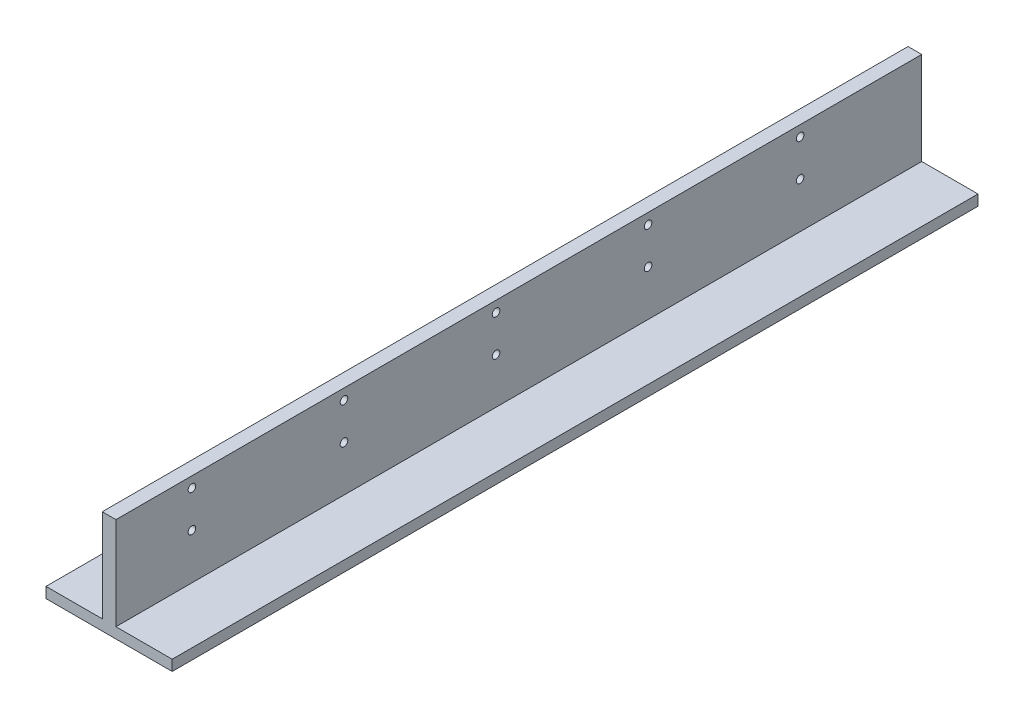
SolidWorks part; units mm, degrees
ref_plane "Plan de face" through (0, 0, 0) normal (0, 0, 1) x (1, 0, 0)
ref_plane "Plan de dessus" through (0, 0, 0) normal (0, 1, 0) x (1, 0, 0)
ref_plane "Plan de droite" through (0, 0, 0) normal (1, 0, 0) x (0, 0, -1)
sketch "Esquisse1" plane through (0, 0, 0) normal (0, 0, 1) x (1, 0, 0)
  line L0 (0, 0) -> (83, 0)
  line L1 (83, 0) -> (83, 7)
  line L2 (83, 7) -> (46, 7)
  line L3 (46, 7) -> (46, 68)
  line L4 (46, 68) -> (37, 68)
  line L5 (37, 68) -> (37, 7)
  line L6 (37, 7) -> (0, 7)
  line L7 (0, 7) -> (0, 0)
  dimension "D1" = 7
  dimension "D2" = 9
  dimension "D3" = 83
  dimension "D4" = 68
extrude "Boss.-Extru.1" add sketch "Esquisse1" along normal blind 530
sketch "Esquisse2" plane through (37, 0, 0) normal (-1, 0, 0) x (0, 0, 1)
  line L0 (0, 49) -> (530, 49) construction
  line L1 (0, 68) -> (0, 7) construction
  line L2 (530, 68) -> (530, 7) construction
  line L3 (530, 68) -> (0, 68) construction
  line L4 (80, 61) -> (180, 61) construction
  circle A0 centre (80, 61) radius 2.5
  circle A1 centre (80, 37) radius 2.5
  circle A2 centre (180, 61) radius 2.5
  circle A3 centre (180, 37) radius 2.5
  circle A4 centre (280, 61) radius 2.5
  circle A5 centre (280, 37) radius 2.5
  circle A6 centre (380, 61) radius 2.5
  circle A7 centre (380, 37) radius 2.5
  circle A8 centre (480, 61) radius 2.5
  circle A9 centre (480, 37) radius 2.5
  dimension "D2" = 12
  dimension "D4" = 5
  dimension "D1" = 19
  dimension "D3" = 80
  dimension "D6" = 100
  dimension "D5" = 5
extrude "Enlèv. mat.-Extru.1" cut sketch "Esquisse2" against normal up to vertex (9 mm away) up to point (46, 68, 0)
